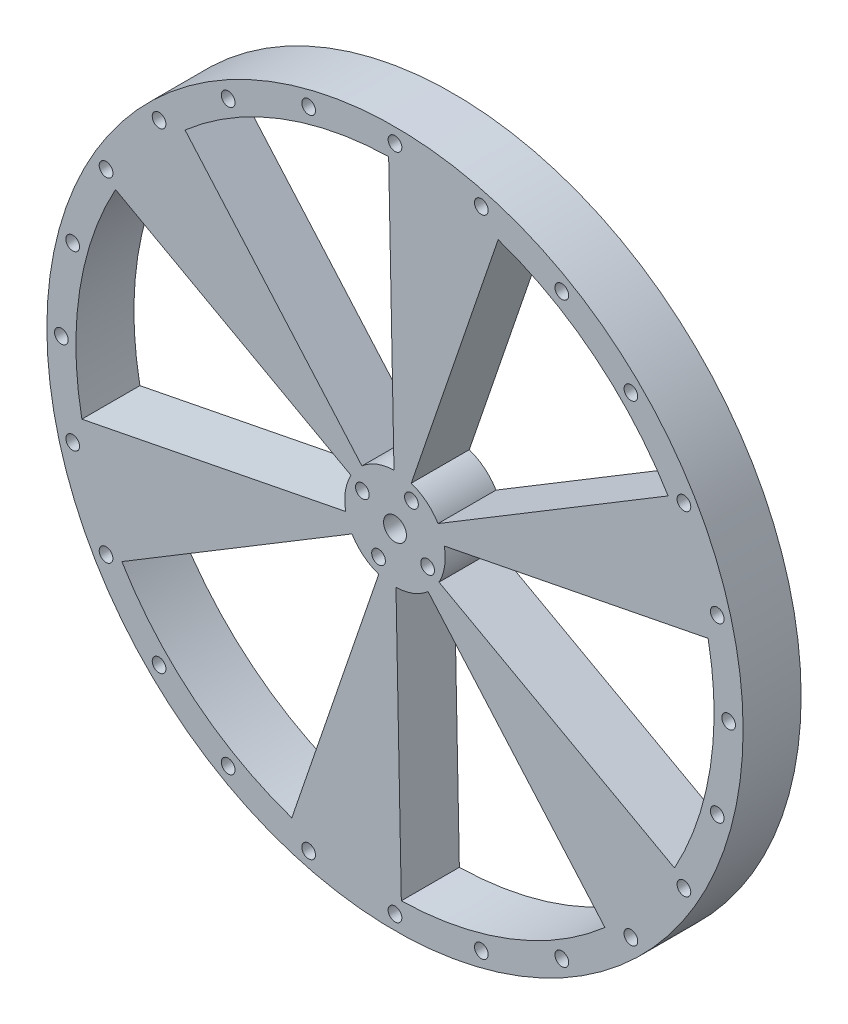
SolidWorks part; units mm, degrees
ref_plane "Front Plane" through (0, 0, 0) normal (0, 0, 1) x (1, 0, 0)
ref_plane "Top Plane" through (0, 0, 0) normal (0, 1, 0) x (1, 0, 0)
ref_plane "Right Plane" through (0, 0, 0) normal (1, 0, 0) x (0, 0, -1)
sketch "Sketch2" plane through (0, 0, 0) normal (0, 0, 1) x (1, 0, 0)
  circle A0 centre (0, 0) radius 76.2
  dimension "D1" = 152.4
extrude "Boss-Extrude1" add sketch "Sketch2" along normal blind 12.7
sketch "Sketch3" plane through (0, 0, 12.7) normal (0, 0, 1) x (1, 0, 0)
  line L0 (-7.2364, 8.2846) -> (-45.9512, 52.6072)
  line L1 (-0.2182, 10.9978) -> (-1.3854, 69.8363)
  line L2 (0, 0) -> (2.1398, 1.2927)
  line L3 (3.5565, 10.4092) -> (22.5836, 66.0985)
  line L4 (0, 0) -> (2.1894, -1.2068)
  line L5 (0, 0) -> (2.4529, 0.4829)
  line L6 (0, 0) -> (0.0496, -2.4995)
  line L7 (0, 0) -> (1.6446, -1.8829)
  line L8 (0, 0) -> (-2.1398, -1.2927)
  line L9 (0, 0) -> (-0.8083, -2.3657)
  line L10 (0, 0) -> (-2.1894, 1.2068)
  line L11 (0, 0) -> (-2.4529, -0.4829)
  line L12 (-9.6335, 5.31) -> (-61.1727, 33.7183)
  line L13 (-10.7929, -2.1246) -> (-68.5347, -13.4913)
  line L14 (-3.5565, -10.4092) -> (-22.5836, -66.0985)
  line L15 (-9.4153, -5.6879) -> (-59.7873, -36.1179)
  line L16 (7.2364, -8.2846) -> (45.9512, -52.6072)
  line L17 (0.2182, -10.9978) -> (1.3854, -69.8363)
  line L18 (9.6335, -5.31) -> (61.1727, -33.7183)
  line L19 (10.7929, 2.1246) -> (68.5347, 13.4913)
  line L20 (9.4153, 5.6879) -> (59.7873, 36.1179)
  arc A0 (-0.2182, 10.9978) -> (-7.2364, 8.2846) centre (0, 0) ccw
  circle A1 centre (0, 0) radius 2.5
  arc A2 (-61.1727, 33.7183) -> (-68.5347, -13.4913) centre (0, 0) ccw
  arc A3 (-1.3854, 69.8363) -> (-45.9512, 52.6072) centre (0, 0) ccw
  arc A4 (-9.6335, 5.31) -> (-10.7929, -2.1246) centre (0, 0) ccw
  arc A5 (-9.4153, -5.6879) -> (-3.5565, -10.4092) centre (0, 0) ccw
  arc A6 (-59.7873, -36.1179) -> (-22.5836, -66.0985) centre (0, 0) ccw
  arc A7 (1.3854, -69.8363) -> (45.9512, -52.6072) centre (0, 0) ccw
  arc A8 (0.2182, -10.9978) -> (7.2364, -8.2846) centre (0, 0) ccw
  arc A9 (9.6335, -5.31) -> (10.7929, 2.1246) centre (0, 0) ccw
  arc A10 (61.1727, -33.7183) -> (68.5347, 13.4913) centre (0, 0) ccw
  arc A11 (59.7873, 36.1179) -> (22.5836, 66.0985) centre (0, 0) ccw
  arc A12 (9.4153, 5.6879) -> (3.5565, 10.4092) centre (0, 0) ccw
  point P16 (0, 0)
  dimension "D1" = 22
  dimension "D2" = 5
  dimension "D3" = 139.7
  dimension "D4" = 40
  dimension "D5" = 69.8363
  dimension "D6" = 6
extrude "Cut-Extrude1" cut sketch "Sketch3" against normal through all contours L1 A3 L0 A0 | A12 L20 A11 L3 | L18 A10 L19 A9 | A8 L17 A7 L16 | L15 A6 L14 A5 | A4 L12 A2 L13 | L2 A1 L10 | L5 A1 L2 | L4 A1 L5 | L7 A1 L4 | L6 A1 L7 | L9 A1 L6 | L8 A1 L9 | L11 A1 L8 | L10 A1 L11 region at (-16.8051, 43.469, 12.7) region at (-0.0273, 1.3781, 12.7) region at (1.6135, -0.2516, 12.7) region at (1.5467, 0.5979, 12.7) region at (0.5889, -1.5232, 12.7) region at (1.2912, -1.0405, 12.7) region at (-1.0247, -1.2715, 12.7) region at (-0.2555, -1.6384, 12.7) region at (-1.6135, 0.2516, 12.7) region at (-1.5467, -0.5979, 12.7) region at (29.2427, 36.2881, 12.7) region at (-46.0478, 7.1809, 12.7) region at (-29.2427, -36.2881, 12.7) region at (16.8051, -43.469, 12.7) region at (46.0478, -7.1809, 12.7)
sketch "Sketch4" plane through (0, 0, 12.7) normal (0, 0, 1) x (1, 0, 0)
  circle A0 centre (0, 0) radius 8 construction
  circle A1 centre (3.6051, 7.1417) radius 1.5
  point P14 (0, 0)
  dimension "D1" = 16
  dimension "D2" = 3
  dimension "D3" = 7.1417
extrude "Cut-Extrude2" cut sketch "Sketch4" against normal through all
pattern_circular "CirPattern1" count 4 over 360 about axis through (0, 0, 12.7) along (0, 0, 1) of "Cut-Extrude2"
sketch "Sketch5" plane through (0, 0, 12.7) normal (0, 0, 1) x (1, 0, 0)
  circle A0 centre (0, 0) radius 73.025 construction
  circle A1 centre (0, 73.025) radius 1.5
  dimension "D1" = 146.05
  dimension "D2" = 3
extrude "Cut-Extrude3" cut sketch "Sketch5" against normal through all
pattern_circular "CirPattern2" count 24 over 360 about axis through (0, 0, 12.7) along (0, 0, 1) of "Cut-Extrude3"
